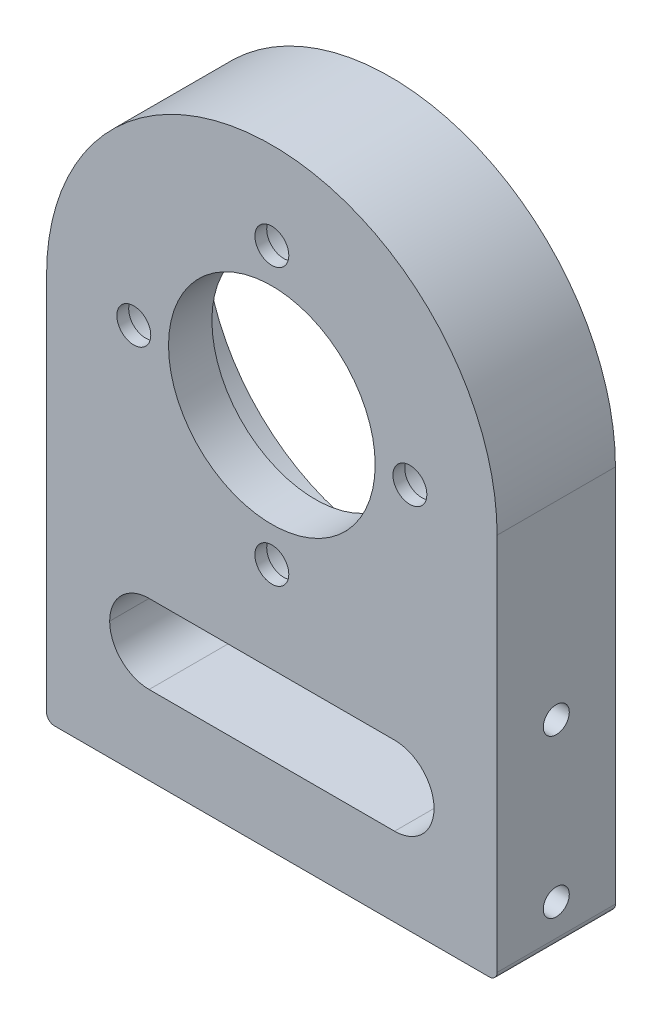
SolidWorks part; units mm, degrees
material "5052-H34"
ref_plane "正面" through (0, 0, 0) normal (0, 0, 1) x (1, 0, 0)
ref_plane "平面" through (0, 0, 0) normal (0, 1, 0) x (1, 0, 0)
ref_plane "右側面" through (0, 0, 0) normal (1, 0, 0) x (0, 0, -1)
sketch "ｽｹｯﾁ1" plane through (0, 0, 0) normal (0, 0, 1) x (1, 0, 0)
  line L0 (0, 0) -> (0, 38) construction
  line L1 (-28.56, -11) -> (28.56, -11)
  line L3 (-28.56, 11) -> (28.56, 11) construction
  line L5 (-28.56, -11) -> (28.56, 11) construction
  line L6 (-28.56, 11) -> (28.56, -11) construction
  line L7 (-28.56, -11) -> (-28.56, 21.3868)
  line L8 (28.56, -11) -> (28.56, 21.3868)
  line L9 (0, 38) -> (33.0405, 38) construction
  line L10 (0, 38) -> (23.3632, 61.3632) construction
  line L11 (-23.3632, 61.3632) -> (0, 38) construction
  arc A0 (28.56, 21.3868) -> (-28.56, 21.3868) centre (0, 38) ccw
  circle A1 centre (0, 38) radius 13.1
  circle A2 centre (0, 38) radius 17.5 construction
  circle A3 centre (0, 55.5) radius 2.15
  circle A4 centre (17.5, 38) radius 2.15
  circle A5 centre (0, 20.5) radius 2.15
  circle A6 centre (-17.5, 38) radius 2.15
  point P0 (0, 0)
  dimension "D4" = 33.0405
  dimension "D5" = 26.2
  dimension "D6" = 35
  dimension "D7" = 4.3
  dimension "D1" = 57.12
  dimension "D2" = 22
  dimension "D3" = 27
  dimension "D9" = 45
  dimension "D12" = 135
  dimension "D8" = 4
extrude "ﾎﾞｽ - 押し出し1" add sketch "ｽｹｯﾁ1" along normal blind 15
sketch "ｽｹｯﾁ2" plane through (28.56, 0, 0) normal (1, 0, 0) x (0, 0, -1)
  line L0 (-7.5, -11) -> (-7.5, 21.3868) construction
  line L1 (-15, -11) -> (0, -11) construction
  line L2 (-15, 21.3868) -> (0, 21.3868) construction
  circle A0 centre (-7.5, -6) radius 1.65
  circle A1 centre (-7.5, 14) radius 1.65
  dimension "D1" = 3.3
  dimension "D3" = 20
  dimension "D2" = 5
extrude "ｶｯﾄ - 押し出し2" cut sketch "ｽｹｯﾁ2" against normal blind 10
ref_plane "平面1" through (0, 0, 0) normal (-1, 0, 0) x (0, 0, 1)
mirror "ﾐﾗｰ2" about plane through (0, 0, 0) normal (-1, 0, 0) of "ｶｯﾄ - 押し出し2"
fillet "ﾌｨﾚｯﾄ3" radius 1 2 edges at (28.56, -11, 7.5) (-28.56, -11, 7.5)
sketch "ｽｹｯﾁ7" plane through (0, 0, 0) normal (0, 0, -1) x (-1, 0, 0)
  circle A0 centre (0, 38) radius 23.5
  dimension "D1" = 47
extrude "ｶｯﾄ - 押し出し7" cut sketch "ｽｹｯﾁ7" against normal blind 9
sketch "ｽｹｯﾁ9" plane through (0, 0, 9) normal (0, 0, -1) x (-1, 0, 0)
  circle A0 centre (0, 38) radius 22.5
  dimension "D1" = 45
extrude "ｶｯﾄ - 押し出し9" cut sketch "ｽｹｯﾁ9" against normal blind 0.5
sketch "ｽｹｯﾁ10" plane through (0, 0, 9.5) normal (0, 0, -1) x (-1, 0, 0)
  circle A0 centre (0, 55.5) radius 4
  circle A1 centre (17.5, 38) radius 4
  circle A2 centre (-17.5, 38) radius 4
  circle A3 centre (0, 20.5) radius 4
  dimension "D1" = 8
extrude "ｶｯﾄ - 押し出し10" cut sketch "ｽｹｯﾁ10" against normal blind 4
sketch "ｽｹｯﾁ11" plane through (0, 0, 0) normal (0, 0, -1) x (-1, 0, 0)
  line L0 (-28.56, 38) -> (-28.56, 5.6934)
  line L1 (-28.56, -10) -> (-28.56, 21.3868) construction
  line L2 (0, 38) -> (0, 0) construction
  line L3 (28.56, 38) -> (28.56, 5.6934)
  line L4 (-28.56, -10) -> (-28.56, 21.3868) construction
  circle A1 centre (0, 38) radius 33.0405
  arc A2 (28.56, 21.3868) -> (-28.56, 21.3868) centre (0, 38) ccw construction
  circle A3 centre (0, 38) radius 28.56
extrude "ｶｯﾄ - 押し出し11" cut sketch "ｽｹｯﾁ11" against normal through all
sketch "ｽｹｯﾁ12" plane through (0, 0, 0) normal (0, 0, -1) x (-1, 0, 0)
  line L0 (27.56, -11) -> (-27.56, -11) construction
  line L1 (20.56, 9) -> (-20.56, 9)
  line L2 (20.56, 9) -> (20.56, -1)
  line L3 (20.56, -1) -> (-20.56, -1)
  line L4 (-20.56, 9) -> (-20.56, -1)
  line L5 (20.56, 9) -> (-20.56, -1) construction
  line L6 (20.56, -1) -> (-20.56, 9) construction
  line L7 (28.56, 38) -> (28.56, -10) construction
  line L8 (-28.56, -10) -> (-28.56, 38) construction
  point P0 (0, 4)
  dimension "D1" = 10
  dimension "D2" = 10
  dimension "D3" = 8
  dimension "D4" = 8
extrude "ｶｯﾄ - 押し出し12" cut sketch "ｽｹｯﾁ12" against normal through all
fillet "ﾌｨﾚｯﾄ4" radius 5 4 edges at (-20.56, 9, 7.5) (-20.56, -1, 7.5) (20.56, 9, 7.5) (20.56, -1, 7.5)
